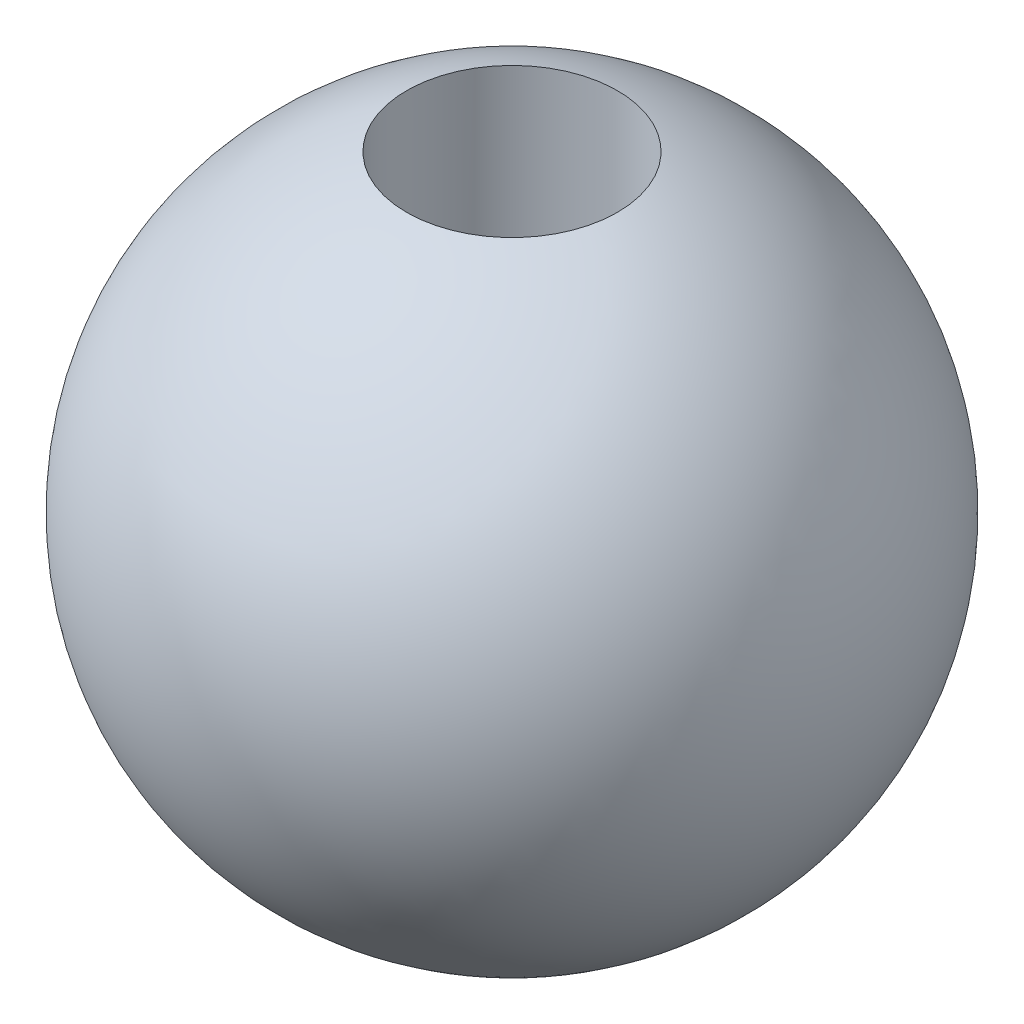
SolidWorks part; units mm, degrees
ref_plane "Vorne" through (0, 0, 0) normal (0, 0, 1) x (1, 0, 0)
ref_plane "Oben" through (0, 0, 0) normal (0, 1, 0) x (1, 0, 0)
ref_plane "Rechts" through (0, 0, 0) normal (1, 0, 0) x (0, 0, -1)
sketch "Skizze1" plane through (0, 0, 0) normal (0, 0, 1) x (1, 0, 0)
  line L0 (0, 12.5) -> (0, -12.5)
  line L1 (0, 27.4263) -> (0, -28.1601) construction
  line L2 (0, -13.027) -> (0, 13.027) construction
  arc A0 (0, 12.5) -> (0, -12.5) centre (0, 0) ccw
  dimension "D1" = 12.5
revolve "Rotation1" add sketch "Skizze1" angle 360 about L1
sketch "Skizze3" plane through (0, 0, 0) normal (0, 1, 0) x (1, 0, 0)
  circle A0 centre (0, 0) radius 4
  dimension "D1" = 8
extrude "Schnitt-Linear austragen1" cut sketch "Skizze3" against normal mid plane 40
sketch "Skizze5" plane through (0, 0, 0) normal (1, 0, 0) x (0, 0, -1)
  line L0 (0, 0) -> (0, 4.8767) construction
  line L1 (-2.15, 0) -> (-2.15, 2)
  line L2 (-2.15, 2) -> (-5, 3.7125)
  line L3 (-5, 3.7125) -> (-5, 0)
  line L4 (-5, 0) -> (-2.15, 0)
  line L5 (13.75, 0) -> (-13.75, 0) construction
  dimension "D1" = 4.3
  dimension "D2" = 59
  dimension "D3" = 10
  dimension "D4" = 2
revolve "Rotation2" add sketch "Skizze5" angle 360 about L0
mirror "Spiegeln1" about plane through (0, 0, 0) normal (0, 1, 0) of "Rotation2"
ref_axis "Achse1" through (13.75, 0, 0) along (-1, 0, 0)
ref_plane "Flexion" through (0, 0, 0) normal (0, 0.9962, -0.0872) x (1, 0, 0)
ref_plane "Extension" through (0, 0, 0) normal (0, 0.9994, 0.0349) x (1, 0, 0)
ref_axis "Achse2" through (0, 0, 14.7952) along (0, 0, -1)
ref_plane "Lateral" through (0, 0, 0) normal (0.0872, 0.9962, 0) x (0.9962, -0.0872, 0)
sketch "Skizze6" [suppressed] plane through (0, 0, 0) normal (0, 1, 0) x (1, 0, 0)
  circle A0 centre (0, 0) radius 5.15
  dimension "D1" = 10.3
extrude "Schnitt-Linear austragen2" [suppressed] cut sketch "Skizze6" against normal through all from offset 2 offset against normal yes
